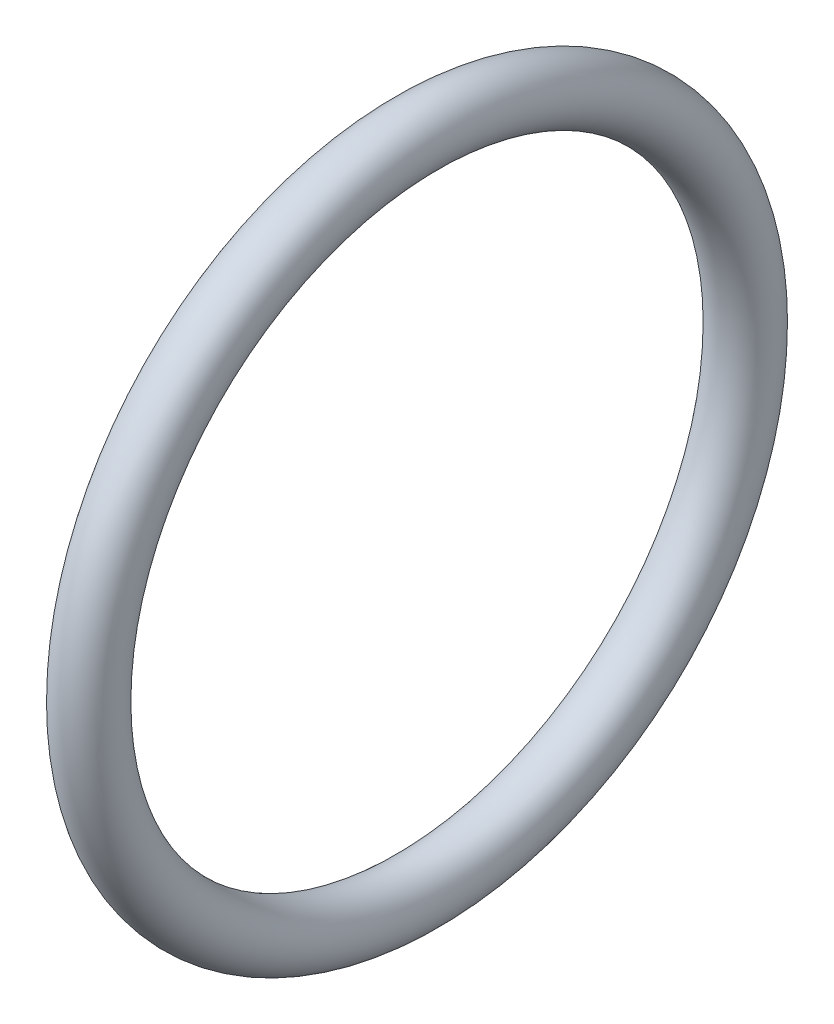
SolidWorks part; units mm, degrees
ref_plane "Front Plane" through (0, 0, 0) normal (0, 0, 1) x (1, 0, 0)
ref_plane "Top Plane" through (0, 0, 0) normal (0, 1, 0) x (1, 0, 0)
ref_plane "Right Plane" through (0, 0, 0) normal (1, 0, 0) x (0, 0, -1)
sketch "Sketch1" plane through (0, 0, 0) normal (0, 0, 1) x (1, 0, 0)
  line L0 (0, 0) -> (0, 76.2) construction
  line L1 (0, 69.85) -> (0, 76.2) construction
  line L2 (0, 0) -> (42.6124, 0) construction
  circle A0 centre (0, 69.85) radius 6.35
  dimension "D2" = 12.7
  dimension "D1" = 76.2
revolve "Revolve1" add sketch "Sketch1" angle 360 about L2
sketch "Sketch2" plane through (0, 0, 0) normal (1, 0, 0) x (0, 0, -1)
  circle A0 centre (0, 0) radius 26.6378 construction
